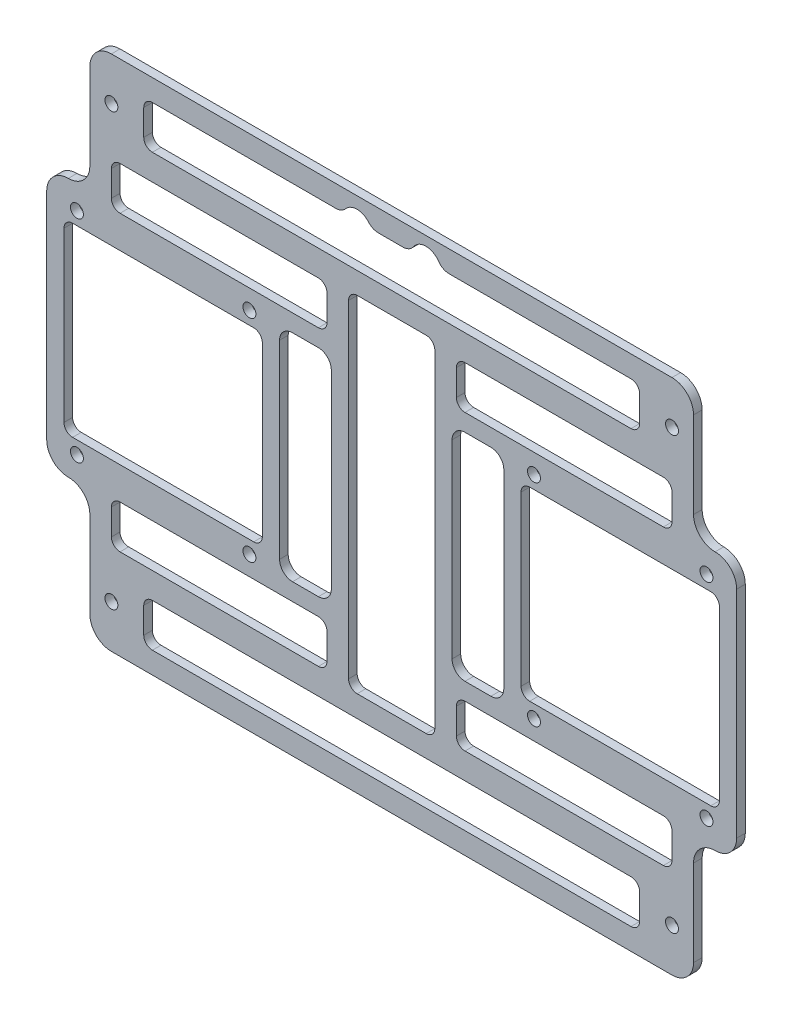
SolidWorks part; units mm, degrees
material "水绿环氧树脂"
ref_plane "前视基准面" through (0, 0, 0) normal (0, 0, 1) x (1, 0, 0)
ref_plane "上视基准面" through (0, 0, 0) normal (0, 1, 0) x (1, 0, 0)
ref_plane "右视基准面" through (0, 0, 0) normal (1, 0, 0) x (0, 0, -1)
sketch "草图1" plane through (0, 0, 0) normal (0, 0, 1) x (1, 0, 0)
  line L1 (-65, -50) -> (65, -50) construction
  line L2 (-65, -50) -> (-65, 50) construction
  line L3 (-65, 50) -> (65, 50) construction
  line L4 (65, -50) -> (65, 50) construction
  line L5 (-65, -50) -> (65, 50) construction
  line L6 (-65, 50) -> (65, -50) construction
  line L7 (-70, -60) -> (70, -60)
  line L8 (-70, -60) -> (-70, -30)
  line L9 (-70, 60) -> (70, 60)
  line L10 (70, -60) -> (70, -30)
  line L11 (-70, -60) -> (70, 60) construction
  line L12 (-70, 60) -> (70, -60) construction
  line L13 (0, 60) -> (0, -60) construction
  line L14 (70, 30) -> (80, 30)
  line L16 (70, -30) -> (80, -30)
  line L17 (80, 30) -> (80, -30)
  line L18 (-80, 30) -> (-80, -30)
  line L19 (-70, -30) -> (-80, -30)
  line L20 (-70, 30) -> (-80, 30)
  line L21 (-70, 30) -> (-70, 60)
  line L22 (70, 30) -> (70, 60)
  circle A0 centre (-65, 50) radius 1.5
  circle A1 centre (65, 50) radius 1.5
  circle A2 centre (65, -50) radius 1.5
  circle A3 centre (-65, -50) radius 1.5
  point P0 (0, 0)
  point P10 (0, 0)
  dimension "D3" = 3
  dimension "D4" = 3
  dimension "D5" = 3
  dimension "D6" = 3
  dimension "D1" = 100
  dimension "D2" = 130
  dimension "D7" = 120
  dimension "D8" = 140
  dimension "D10" = 60
  dimension "D11" = 10
extrude "凸台-拉伸1" add sketch "草图1" along normal blind 2
sketch "草图2" plane through (0, 0, 2) normal (0, 0, 1) x (1, 0, 0)
  line L0 (-18, 0) -> (-88, 0) construction
  line L2 (18, 0) -> (88, 0) construction
  line L3 (-73, -24.5) -> (-33, -24.5) construction
  line L4 (-73, -24.5) -> (-73, 24.5) construction
  line L5 (-73, 24.5) -> (-33, 24.5) construction
  line L6 (-33, -24.5) -> (-33, 24.5) construction
  line L7 (-73, -24.5) -> (-33, 24.5) construction
  line L8 (-73, 24.5) -> (-33, -24.5) construction
  line L11 (33, -24.5) -> (73, -24.5) construction
  line L12 (33, -24.5) -> (33, 24.5) construction
  line L13 (33, 24.5) -> (73, 24.5) construction
  line L14 (73, -24.5) -> (73, 24.5) construction
  line L15 (33, -24.5) -> (73, 24.5) construction
  line L16 (33, 24.5) -> (73, -24.5) construction
  line L17 (30, -21.5) -> (76, -21.5)
  line L18 (30, -21.5) -> (30, 21.5)
  line L19 (30, 21.5) -> (76, 21.5)
  line L20 (76, -21.5) -> (76, 21.5)
  line L21 (30, -21.5) -> (76, 21.5) construction
  line L22 (30, 21.5) -> (76, -21.5) construction
  line L23 (-76, -21.5) -> (-30, -21.5)
  line L24 (-76, -21.5) -> (-76, 21.5)
  line L25 (-76, 21.5) -> (-30, 21.5)
  line L26 (-30, -21.5) -> (-30, 21.5)
  line L27 (-76, -21.5) -> (-30, 21.5) construction
  line L28 (-76, 21.5) -> (-30, -21.5) construction
  circle A0 centre (-73, 24.5) radius 1.5
  circle A1 centre (-33, 24.5) radius 1.5
  circle A2 centre (-73, -24.5) radius 1.5
  circle A3 centre (-33, -24.5) radius 1.5
  circle A4 centre (33, 24.5) radius 1.5
  circle A5 centre (73, 24.5) radius 1.5
  circle A6 centre (33, -24.5) radius 1.5
  circle A7 centre (73, -24.5) radius 1.5
  point P5 (-53, 0)
  point P10 (53, 0)
  point P26 (53, 0)
  point P31 (-53, 0)
  dimension "D5" = 3
  dimension "D6" = 3
  dimension "D7" = 3
  dimension "D8" = 3
  dimension "D9" = 3
  dimension "D10" = 3
  dimension "D11" = 3
  dimension "D12" = 3
  dimension "D1" = 49
  dimension "D2" = 40
  dimension "D3" = 49
  dimension "D4" = 40
  dimension "D13" = 43
  dimension "D14" = 46
  dimension "D15" = 43
  dimension "D16" = 46
extrude "切除-拉伸1" cut sketch "草图2" against normal blind 2
fillet "圆角1" radius 2 8 edges at (-30, -21.5, 1) (-76, -21.5, 1) (-76, 21.5, 1) (-30, 21.5, 1) (76, -21.5, 1) (76, 21.5, 1) (30, -21.5, 1) (30, 21.5, 1)
sketch "草图3" plane through (0, 0, 2) normal (0, 0, 1) x (1, 0, 0)
  line L0 (-65, -50) -> (65, -50) construction
  line L2 (-57.5, -55) -> (57.5, -55)
  line L3 (-57.5, -55) -> (-57.5, -45)
  line L4 (-57.5, -45) -> (57.5, -45)
  line L5 (57.5, -55) -> (57.5, -45)
  line L6 (-57.5, -55) -> (57.5, -45) construction
  line L7 (-57.5, -45) -> (57.5, -55) construction
  line L10 (-57.5, 45) -> (57.5, 55) construction
  line L11 (-57.5, 55) -> (57.5, 45) construction
  line L12 (-65, 50) -> (65, 50) construction
  line L13 (57.5, 55) -> (57.5, 45)
  line L14 (-57.5, 45) -> (57.5, 45)
  line L15 (-57.5, 55) -> (-57.5, 45)
  line L16 (-57.5, 55) -> (57.5, 55)
  point P4 (0, -50)
  point P21 (0, 50)
  dimension "D1" = 10
  dimension "D2" = 115
extrude "切除-拉伸2" cut sketch "草图3" against normal blind 2
fillet "圆角2" radius 2 8 edges at (57.5, 55, 1) (57.5, 45, 1) (57.5, -55, 1) (-57.5, -55, 1) (-57.5, -45, 1) (57.5, -45, 1) (-57.5, 55, 1) (-57.5, 45, 1)
sketch "草图4" plane through (0, 0, 2) normal (0, 0, 1) x (1, 0, 0)
  line L0 (10, 45) -> (10, 23) construction
  line L1 (-10, -40) -> (10, -40)
  line L2 (-10, -40) -> (-10, 40)
  line L3 (-10, 40) -> (10, 40)
  line L4 (10, -40) -> (10, 40)
  line L5 (-10, -40) -> (10, 40) construction
  line L6 (-10, 40) -> (10, -40) construction
  line L7 (-55.5, 45) -> (55.5, 45) construction
  line L8 (10, 23) -> (10, 34) construction
  line L9 (10, 34) -> (70, 34) construction
  line L10 (70, -60) -> (70, -30) construction
  line L11 (0, 55) -> (0, 45) construction
  line L12 (15, 29) -> (65, 29)
  line L13 (15, 29) -> (15, 39)
  line L14 (15, 39) -> (65, 39)
  line L15 (65, 29) -> (65, 39)
  line L16 (15, 29) -> (65, 39) construction
  line L17 (15, 39) -> (65, 29) construction
  line L18 (55.5, 55) -> (-55.5, 55) construction
  line L19 (-15, 39) -> (-65, 29) construction
  line L20 (-15, 29) -> (-65, 39) construction
  line L21 (-10, 34) -> (-70, 34) construction
  line L22 (-65, 29) -> (-65, 39)
  line L23 (-15, 39) -> (-65, 39)
  line L24 (-15, 29) -> (-15, 39)
  line L25 (-15, 29) -> (-65, 29)
  line L26 (-76, 0) -> (-30, 0) construction
  line L27 (-76, 19.5) -> (-76, -19.5) construction
  line L28 (-30, -19.5) -> (-30, 19.5) construction
  line L29 (65, -29) -> (65, -39)
  line L30 (15, -39) -> (65, -39)
  line L31 (15, -29) -> (15, -39)
  line L32 (15, -29) -> (65, -29)
  line L33 (-10, -34) -> (-70, -34) construction
  line L34 (-15, -29) -> (-65, -39) construction
  line L35 (-15, -39) -> (-65, -29) construction
  line L36 (-15, -29) -> (-65, -29)
  line L37 (-15, -29) -> (-15, -39)
  line L38 (-15, -39) -> (-65, -39)
  line L39 (-65, -29) -> (-65, -39)
  point P0 (0, 0)
  point P11 (40, 34)
  point P29 (-40, 34)
  point P46 (-40, -34)
  dimension "D1" = 80
  dimension "D2" = 20
  dimension "D3" = 10
  dimension "D4" = 50
extrude "切除-拉伸3" cut sketch "草图4" against normal blind 2
fillet "圆角3" radius 2 20 edges at (10, -40, 1) (-10, -40, 1) (65, 29, 1) (15, 29, 1) (15, 39, 1) (65, 39, 1) (-15, 29, 1) (-65, 29, 1) (-65, 39, 1) (-15, 39, 1) (65, -29, 1) (65, -39, 1) (15, -39, 1) (15, -29, 1) (-15, -39, 1) (-65, -39, 1) (-65, -29, 1) (-15, -29, 1) (10, 40, 1) (-10, 40, 1)
fillet "圆角4" radius 5 12 edges at (70, -60, 1) (-70, -60, 1) (70, 30, 1) (80, 30, 1) (80, -30, 1) (70, -30, 1) (-70, -30, 1) (-80, -30, 1) (-80, 30, 1) (-70, 30, 1) (70, 60, 1) (-70, 60, 1)
sketch "草图5" plane through (0, 0, 2) normal (0, 0, 1) x (1, 0, 0)
  circle A6 centre (-8.0368, 53.7788) radius 3.5
  circle A7 centre (7.9531, 54.3472) radius 3.5
extrude "切除-拉伸4" cut sketch "草图5" against normal blind 2
sketch "草图6" plane through (0, 0, 2) normal (0, 0, 1) x (1, 0, 0)
  line L0 (-30, 0) -> (-10, 0) construction
  line L1 (-30, -19.5) -> (-30, 19.5) construction
  line L2 (-10, 38) -> (-10, -38) construction
  line L3 (10, 0) -> (30, 0) construction
  line L4 (10, -38) -> (10, 38) construction
  line L5 (30, 19.5) -> (30, -19.5) construction
  line L6 (0, -40) -> (0, 27.1935) construction
  line L7 (14, -25) -> (26, -25)
  line L8 (14, -25) -> (14, 25)
  line L9 (14, 25) -> (26, 25)
  line L10 (26, -25) -> (26, 25)
  line L11 (14, -25) -> (26, 25) construction
  line L12 (14, 25) -> (26, -25) construction
  line L13 (-8, -40) -> (8, -40) construction
  line L14 (-14, 25) -> (-26, -25) construction
  line L15 (-14, -25) -> (-26, 25) construction
  line L16 (-10, 0) -> (-30, 0) construction
  line L17 (-26, -25) -> (-26, 25)
  line L18 (-14, 25) -> (-26, 25)
  line L19 (-14, -25) -> (-14, 25)
  line L20 (-14, -25) -> (-26, -25)
  point P12 (20, 0)
  point P26 (-20, 0)
  dimension "D1" = 50
  dimension "D2" = 12
extrude "切除-拉伸5" cut sketch "草图6" against normal blind 2
fillet "圆角5" radius 3 12 edges at (-4.7568, 55, 1) (4.5145, 55, 1) (11.3916, 55, 1) (-11.3169, 55, 1) (-14, -25, 1) (-26, -25, 1) (26, -25, 1) (14, -25, 1) (14, 25, 1) (26, 25, 1) (-14, 25, 1) (-26, 25, 1)
